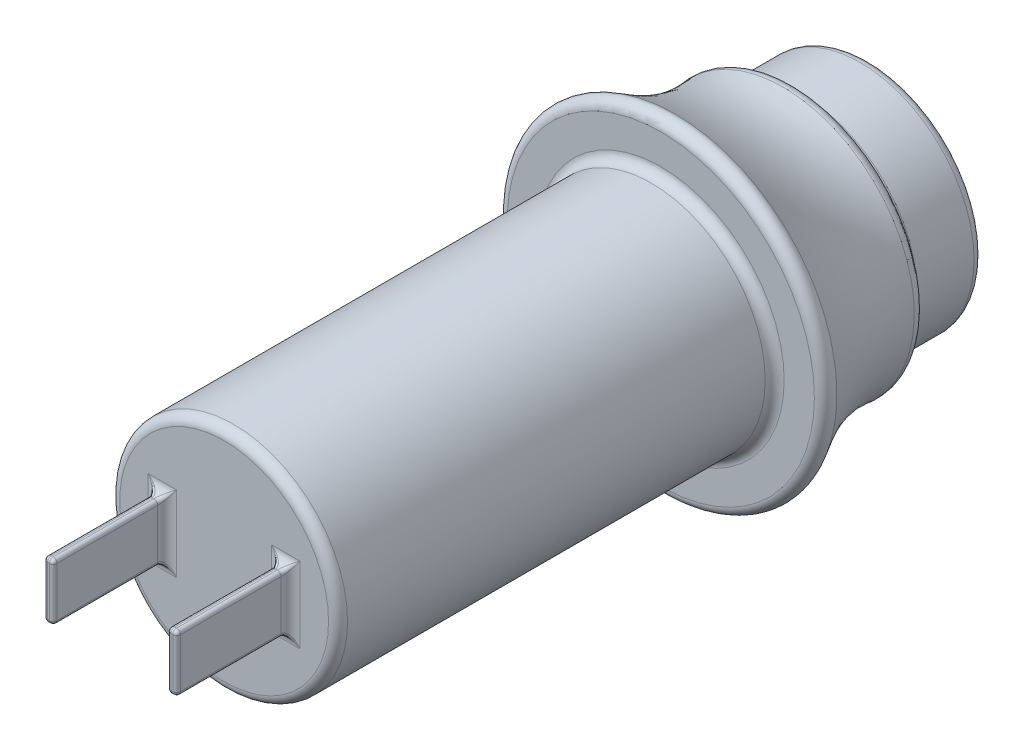
SolidWorks part; units mm, degrees
ref_plane "Front Plane" through (0, 0, 0) normal (0, 0, 1) x (1, 0, 0)
ref_plane "Top Plane" through (0, 0, 0) normal (0, 1, 0) x (1, 0, 0)
ref_plane "Right Plane" through (0, 0, 0) normal (1, 0, 0) x (0, 0, -1)
sketch "Sketch1" plane through (0, 0, 0) normal (0, 0, 1) x (1, 0, 0)
  circle A0 centre (0, 0) radius 6
  dimension "D1" = 12
extrude "Boss-Extrude1" add sketch "Sketch1" along normal blind 4
sketch "Sketch2" plane through (0, 0, 4) normal (0, 0, 1) x (1, 0, 0)
  circle A0 centre (0, 0) radius 7
ref_plane "Plane1" through (0, 0, 11) normal (0, 0, 1) x (1, 0, 0)
sketch "Sketch3" plane through (0, 0, 11) normal (0, 0, 1) x (1, 0, 0)
  circle A0 centre (0, 0) radius 9
  dimension "D1" = 18
loft "Loft1" add profiles "Sketch3", "Sketch2" connector at (-8.5938, 2.6734, 11) connector at (-2.5072, 6.5356, 4)
sketch "Sketch4" plane through (0, 0, 11) normal (0, 0, 1) x (1, 0, 0)
  circle A0 centre (0, 0) radius 6
  dimension "D1" = 12
extrude "Boss-Extrude2" add sketch "Sketch4" along normal blind 23
sketch "Sketch5" plane through (0, 0, 34) normal (0, 0, 1) x (1, 0, 0)
  line L0 (0, 0) -> (0, 2.8983) construction
  line L1 (-3.5, 1.5) -> (-3, 1.5)
  line L2 (-3.5, 1.5) -> (-3.5, -1.5)
  line L3 (-3.5, -1.5) -> (-3, -1.5)
  line L4 (-3, 1.5) -> (-3, -1.5)
  line L5 (3, 1.5) -> (3, -1.5)
  line L6 (3.5, -1.5) -> (3, -1.5)
  line L7 (3.5, 1.5) -> (3.5, -1.5)
  line L8 (3.5, 1.5) -> (3, 1.5)
  point P4 (-3, 0)
  dimension "D1" = 0.5
  dimension "D2" = 3
  dimension "D3" = 3
extrude "Boss-Extrude3" add sketch "Sketch5" along normal blind 6
fillet "Fillet1" radius 0.5 3 edges at (6, 0, 0) (7, 0, 4) (9, 0, 11)
fillet "Fillet2" radius 0.5 1 edges at (6, 0, 4)
fillet "Fillet3" radius 0.5 2 edges at (6, 0, 11) (6, 0, 34)
fillet "Fillet4" radius 0.5 4 edges at (3.25, 1.5, 34) (3.5, 0, 34) (3.25, -1.5, 34) (3, 0, 34)
fillet "Fillet5" radius 0.5 4 edges at (-3.5, 0, 34) (-3.25, -1.5, 34) (-3, 0, 34) (-3.25, 1.5, 34)
fillet "Fillet6" radius 0.2 24 edges at (-3.6464, -1.6464, 34.1464) (-2.8536, -1.6464, 34.1464) (-3.6464, 1.6464, 34.1464) (-2.8536, 1.6464, 34.1464) (2.8536, 1.6464, 34.1464) (2.8536, -1.6464, 34.1464) (3.6464, 1.6464, 34.1464) (3.6464, -1.6464, 34.1464) (-3.5, -1.5, 37.25) (-3, -1.5, 37.25) (-3.5, 1.5, 37.25) (-3, 1.5, 37.25) (-3.25, 1.5, 40) (-3, 0, 40) (-3.25, -1.5, 40) (-3.5, 0, 40) (3, 1.5, 37.25) (3, -1.5, 37.25) (3.5, 1.5, 37.25) (3.5, -1.5, 37.25) (3.5, 0, 40) (3.25, -1.5, 40) (3, 0, 40) (3.25, 1.5, 40)
